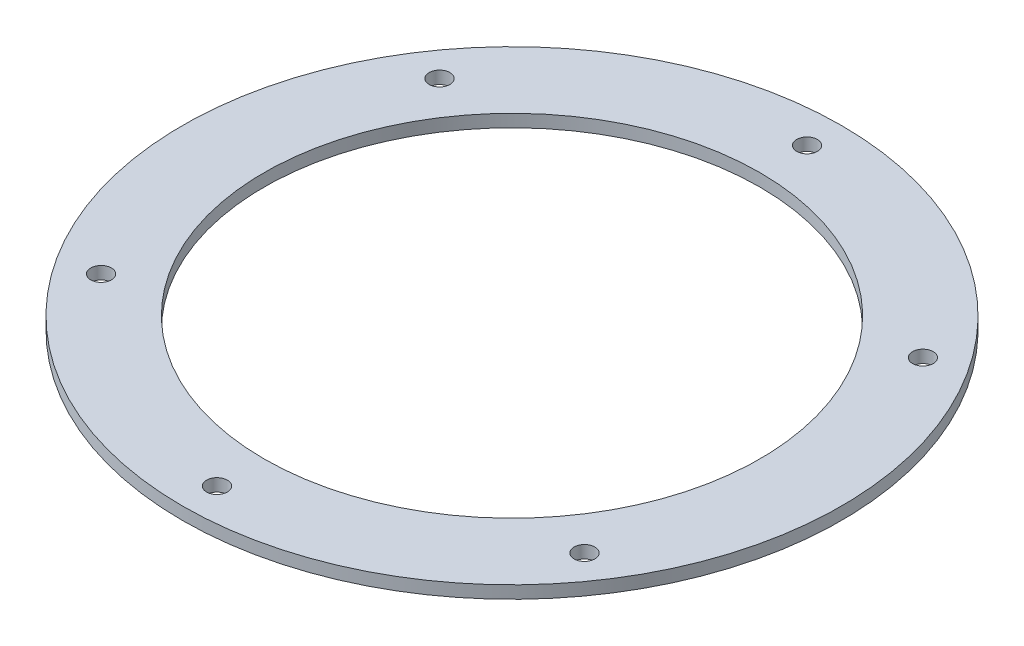
SolidWorks part; units mm, degrees
ref_plane "Front Plane" through (0, 0, 0) normal (0, 0, 1) x (1, 0, 0)
ref_plane "Top Plane" through (0, 0, 0) normal (0, 1, 0) x (1, 0, 0)
ref_plane "Right Plane" through (0, 0, 0) normal (1, 0, 0) x (0, 0, -1)
sketch "Sketch1" plane through (0, 0, 0) normal (0, 1, 0) x (1, 0, 0)
  circle A0 centre (0, 0) radius 39.5
  circle A1 centre (0, 0) radius 52.5
  dimension "D1" = 79
  dimension "D2" = 105
extrude "Boss-Extrude1" add sketch "Sketch1" along normal blind 2
sketch "Sketch2" plane through (0, 2, 0) normal (0, 1, 0) x (1, 0, 0)
  line L0 (0, 0) -> (-52.5, 0) construction
  line L1 (0, 0) -> (-43.0055, 30.1128) construction
  line L2 (0, 0) -> (43.0055, 30.1128) construction
  line L3 (0, 0) -> (43.0055, -30.1128) construction
  line L4 (0, 0) -> (-43.0055, -30.1128) construction
  line L5 (0, 0) -> (0, 39.5) construction
  line L6 (0, 0) -> (52.5, 0) construction
  circle A1 centre (0, 47) radius 1.65
  circle A4 centre (0, -47) radius 1.65
  circle A5 centre (0, 0) radius 52.5 construction
  circle A7 centre (-38.5001, 26.9581) radius 1.65
  circle A8 centre (38.5001, 26.9581) radius 1.65
  circle A9 centre (38.5001, -26.9581) radius 1.65
  circle A10 centre (-38.5001, -26.9581) radius 1.65
  circle A11 centre (0, 0) radius 39.5 construction
  dimension "D1" = 47
  dimension "D2" = 3.3
  dimension "D3" = 47
  dimension "D4" = 47
  dimension "D5" = 47
  dimension "D6" = 47
  dimension "D7" = 47
  dimension "D8" = 35
  dimension "D9" = 35
  dimension "D10" = 35
  dimension "D11" = 35
extrude "Cut-Extrude1" cut sketch "Sketch2" against normal blind 2
